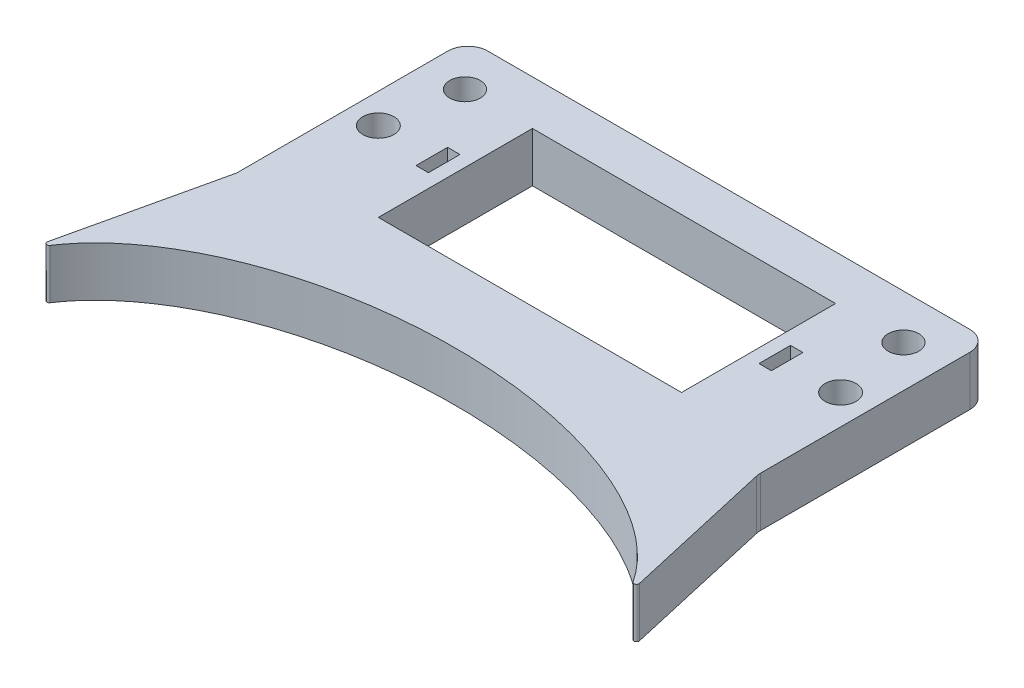
SolidWorks part; units mm, degrees
ref_plane "Front Plane" through (0, 0, 0) normal (0, 0, 1) x (1, 0, 0)
ref_plane "Top Plane" through (0, 0, 0) normal (0, 1, 0) x (1, 0, 0)
ref_plane "Right Plane" through (0, 0, 0) normal (1, 0, 0) x (0, 0, -1)
sketch "Sketch1" plane through (0, 0, 0) normal (0, 1, 0) x (1, 0, 0)
  line L1 (-52.5, -27.5) -> (52.5, -27.5)
  line L2 (-52.5, -27.5) -> (-52.5, 27.5)
  line L3 (-52.5, 27.5) -> (52.5, 27.5)
  line L4 (52.5, -27.5) -> (52.5, 27.5)
  line L5 (0, 27.5) -> (0, -27.5) construction
  line L6 (-52.5, 0) -> (52.5, 0) construction
  point P0 (0, 0)
  dimension "D1" = 105
  dimension "D2" = 55
extrude "Boss-Extrude1" add sketch "Sketch1" along normal blind 10
sketch "Sketch2" plane through (0, 10, 0) normal (0, 1, 0) x (1, 0, 0)
  line L6 (-30.5, 18.5) -> (30.5, 18.5)
  line L7 (-30.5, 18.5) -> (-30.5, -12.5)
  line L8 (-30.5, -12.5) -> (30.5, -12.5)
  line L9 (30.5, 18.5) -> (30.5, -12.5)
  line L10 (0, -12.5) -> (0, 18.5) construction
  line L11 (-30.5, 3) -> (30.5, 3) construction
  line L12 (0, 0) -> (0, -12.5) construction
  line L14 (-52.5, -27.5) -> (52.5, -27.5) construction
  point P0 (0, 3)
  dimension "D1" = 31
  dimension "D2" = 61
  dimension "D3" = 15
extrude "Cut-Extrude1" cut sketch "Sketch2" against normal through all
sketch "Sketch4" plane through (0, 10, 0) normal (0, 1, 0) x (1, 0, 0)
  line L2 (-46.5, 3.5) -> (-34.5, 3.5) construction
  line L3 (30.5, 18.5) -> (-30.5, 18.5) construction
  line L4 (-33.25, 6.675) -> (-35.75, 6.675)
  line L5 (-33.25, 6.675) -> (-33.25, 0.325)
  line L6 (-33.25, 0.325) -> (-35.75, 0.325)
  line L7 (-35.75, 6.675) -> (-35.75, 0.325)
  line L8 (-34.5, 0.325) -> (-34.5, 6.675) construction
  line L9 (-33.25, 3.5) -> (-35.75, 3.5) construction
  line L10 (-30.5, 18.5) -> (-30.5, -12.5) construction
  circle A0 centre (-46.5, 3.5) radius 3.125
  dimension "D1" = 6.25
  dimension "D2" = 15
  dimension "D3" = 16
  dimension "D4" = 2.5
  dimension "D5" = 6.35
  dimension "D6" = 2.75
extrude "Cut-Extrude3" cut sketch "Sketch4" against normal through all
sketch "Sketch5" plane through (0, 0, 0) normal (0, 1, 0) x (1, 0, 0)
  line L0 (0, 0) -> (0, -62.5) construction
  line L1 (-52.5, -27.5) -> (52.5, -27.5) construction
  line L2 (-52.5, -19.0391) -> (-60.2822, -53.2591)
  line L3 (-52.5, 27.5) -> (-52.5, -27.5) construction
  line L4 (-52.5, -19.0391) -> (0, -27.5)
  ellipse E0 centre (0, -62.5) end of major axis (-62.5, -62.5) minor radius 35
  dimension "D1" = 125
  dimension "D2" = 62.5
extrude "Boss-Extrude2" add sketch "Sketch5" along normal up to surface (10 mm away) contours E0 L4 L2 region at (-40.4501, 0, 30.082) up to face at (-46.5, 10, -0.375)
sketch "Sketch6" plane through (0, 10, 0) normal (0, 1, 0) x (1, 0, 0)
  circle A0 centre (-44.1085, 18.5417) radius 3.075
  dimension "D1" = 6.15
extrude "Cut-Extrude4" cut sketch "Sketch6" against normal through all
mirror "Mirror1" about plane through (0, 0, 0) normal (1, 0, 0) of "Cut-Extrude4", "Boss-Extrude2", "Cut-Extrude3"
fillet "Fillet1" radius 4 4 edges at (-52.5, 5, 19.0391) (52.5, 5, 19.0391) (52.5, 5, -27.5) (-52.5, 5, -27.5)
fillet "Fillet2" radius 0.5 2 edges at (60.2822, 5, 53.2591) (-60.2822, 5, 53.2591)
